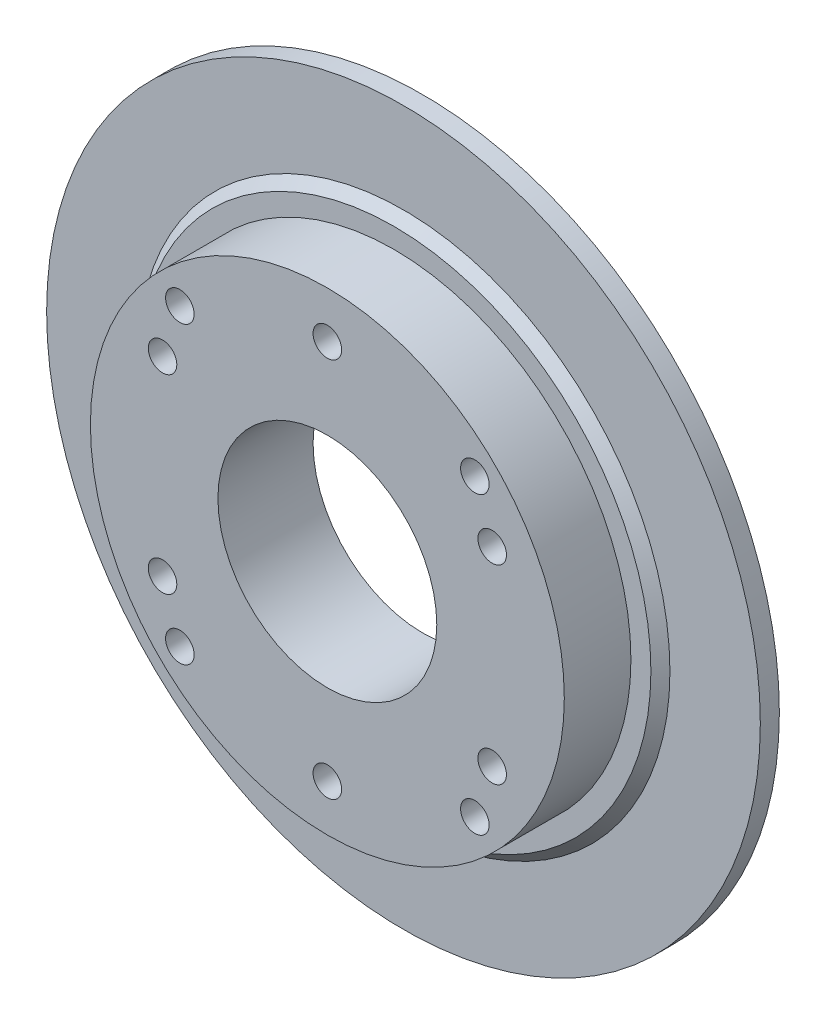
SolidWorks part; units mm, degrees
ref_plane "Front Plane" through (0, 0, 0) normal (0, 0, 1) x (1, 0, 0)
ref_plane "Top Plane" through (0, 0, 0) normal (0, 1, 0) x (1, 0, 0)
ref_plane "Right Plane" through (0, 0, 0) normal (1, 0, 0) x (0, 0, -1)
sketch "Sketch1" plane through (0, 0, 0) normal (0, 0, 1) x (1, 0, 0)
  circle A0 centre (0, 0) radius 37.5
  dimension "D1" = 75
extrude "Boss-Extrude1" add sketch "Sketch1" along normal blind 2
sketch "Sketch5" plane through (0, 0, 2) normal (0, 0, 1) x (1, 0, 0)
  circle A0 centre (0, 0) radius 28
  dimension "D1" = 56
extrude "Boss-Extrude5" add sketch "Sketch5" along normal blind 1
sketch "Sketch2" plane through (0, 0, 3) normal (0, 0, 1) x (1, 0, 0)
  circle A0 centre (0, 0) radius 24.9
  dimension "D1" = 49.8
extrude "Boss-Extrude2" add sketch "Sketch2" along normal blind 7
sketch "Sketch3" plane through (0, 0, 10) normal (0, 0, 1) x (1, 0, 0)
  circle A0 centre (0, 0) radius 11.5
  dimension "D1" = 23
extrude "Cut-Extrude1" cut sketch "Sketch3" against normal through all
sketch "Sketch4" plane through (0, 0, 10) normal (0, 0, 1) x (1, 0, 0)
  circle A0 centre (-15.5, 15.5) radius 1.5
  circle A1 centre (15.5, 15.5) radius 1.5
  circle A2 centre (15.5, -15.5) radius 1.5
  circle A3 centre (-15.5, -15.5) radius 1.5
  dimension "D5" = 3
  dimension "D1" = 15.5
  dimension "D4" = 15.5
  dimension "D2" = 2
  dimension "D3" = 2
extrude "Cut-Extrude2" cut sketch "Sketch4" against normal through all
chamfer "Chamfer1" distance 1 distance2 1 1 edges at (28, 0, 3)
sketch "Sketch6" plane through (0, 0, 10) normal (0, 0, 1) x (1, 0, 0)
  line L0 (0, 0) -> (-17.3205, -10) construction
  line L1 (0, 0) -> (0, -20) construction
  arc A0 (-1.4989, -19.9437) -> (1.4989, -19.9438) centre (0, 0) ccw
  circle A1 centre (-17.3205, -10) radius 1.5
  circle A2 centre (-17.3205, 10) radius 1.5
  circle A3 centre (0, 20) radius 1.5
  circle A4 centre (17.3205, 10) radius 1.5
  circle A5 centre (17.3205, -10) radius 1.5
  circle A6 centre (0, -20) radius 1.5
  point P18 (0, 0)
  dimension "D1" = 40
  dimension "D3" = 3
  dimension "D2" = 60
  dimension "D4" = 6
extrude "Cut-Extrude3" cut sketch "Sketch6" against normal blind 3 contours A3 | A1 | A6 | A5 | A4 | A2 region at (0, 20, 10)
